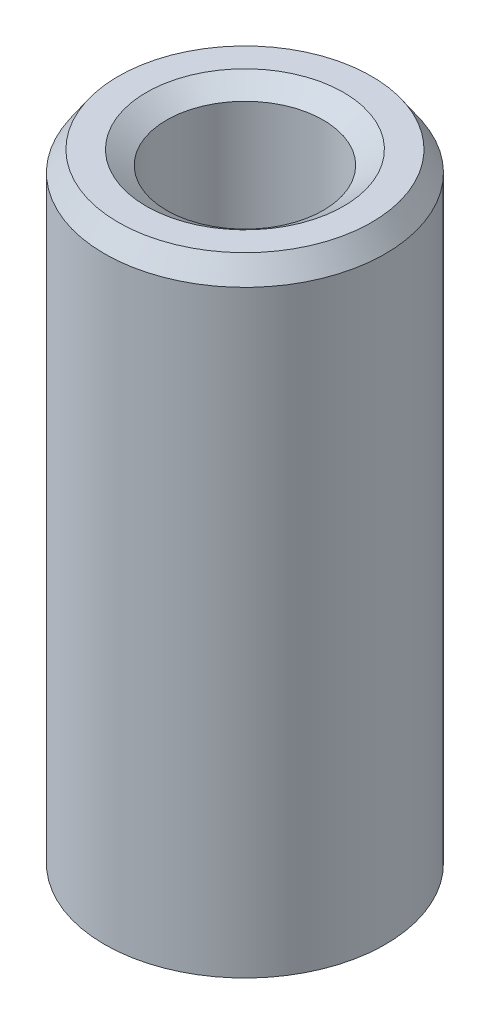
SolidWorks part; units mm, degrees
ref_plane "Front Plane" through (0, 0, 0) normal (0, 0, 1) x (1, 0, 0)
ref_plane "Top Plane" through (0, 0, 0) normal (0, 1, 0) x (1, 0, 0)
ref_plane "Right Plane" through (0, 0, 0) normal (1, 0, 0) x (0, 0, -1)
sketch "Sketch1" plane through (0, 0, 0) normal (0, 1, 0) x (1, 0, 0)
  circle A0 centre (0, 0) radius 10
  dimension "SLEEVE_OD" = 20
extrude "Boss-Extrude1" add sketch "Sketch1" along normal blind 45.0358
sketch "Sketch2" plane through (0, 0, 0) normal (0, 1, 0) x (1, 0, 0)
  circle A0 centre (0, 0) radius 5.5797
  dimension "BORE_D" = 11.1595
extrude "Cut-Extrude1" cut sketch "Sketch2" along normal through all
chamfer "Chamfer1" distance 1.447 angle 34.107 4 edges at (0, 45.0358, 5.5797) (0, 0, 5.5797) (0, 0, 10) (0, 45.0358, 10) first distance on face at (0, 45.0358, 5.5797) first distance on face at (0, 0, 5.5797) first distance on face at (0, 45.0358, 10)
